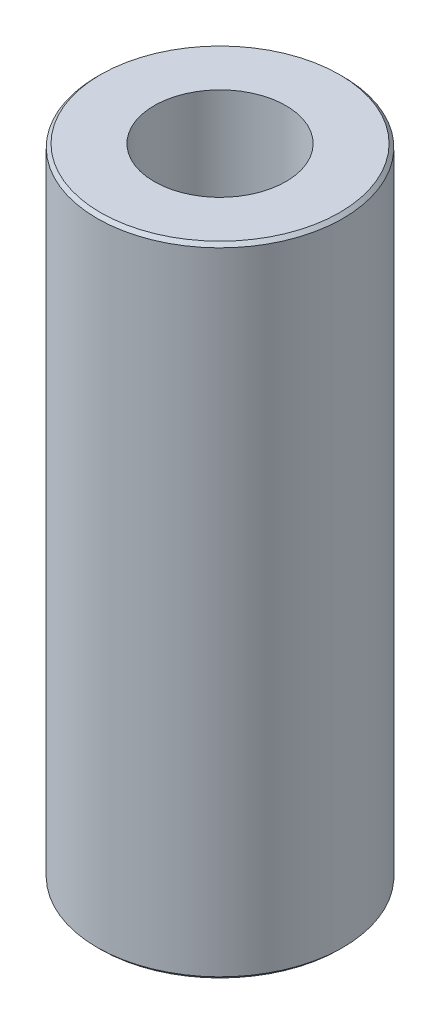
SolidWorks part; units mm, degrees
ref_plane "Front Plane" through (0, 0, 0) normal (0, 0, 1) x (1, 0, 0)
ref_plane "Top Plane" through (0, 0, 0) normal (0, 1, 0) x (1, 0, 0)
ref_plane "Right Plane" through (0, 0, 0) normal (1, 0, 0) x (0, 0, -1)
sketch "Sketch1" plane through (0, 0, 0) normal (0, 1, 0) x (1, 0, 0)
  circle A0 centre (0, 0) radius 60
  dimension "SHAFT_OD" = 120
extrude "Boss-Extrude1" add sketch "Sketch1" along normal blind 311.4628
sketch "Sketch2" plane through (0, 0, 0) normal (0, 1, 0) x (1, 0, 0)
  circle A0 centre (0, 0) radius 32.1489
  dimension "BORE_D" = 64.2979
extrude "Cut-Extrude1" cut sketch "Sketch2" along normal through all
chamfer "Chamfer1" distance 1.6499 angle 45 2 edges at (0, 311.4628, 60) (0, 0, 60)
